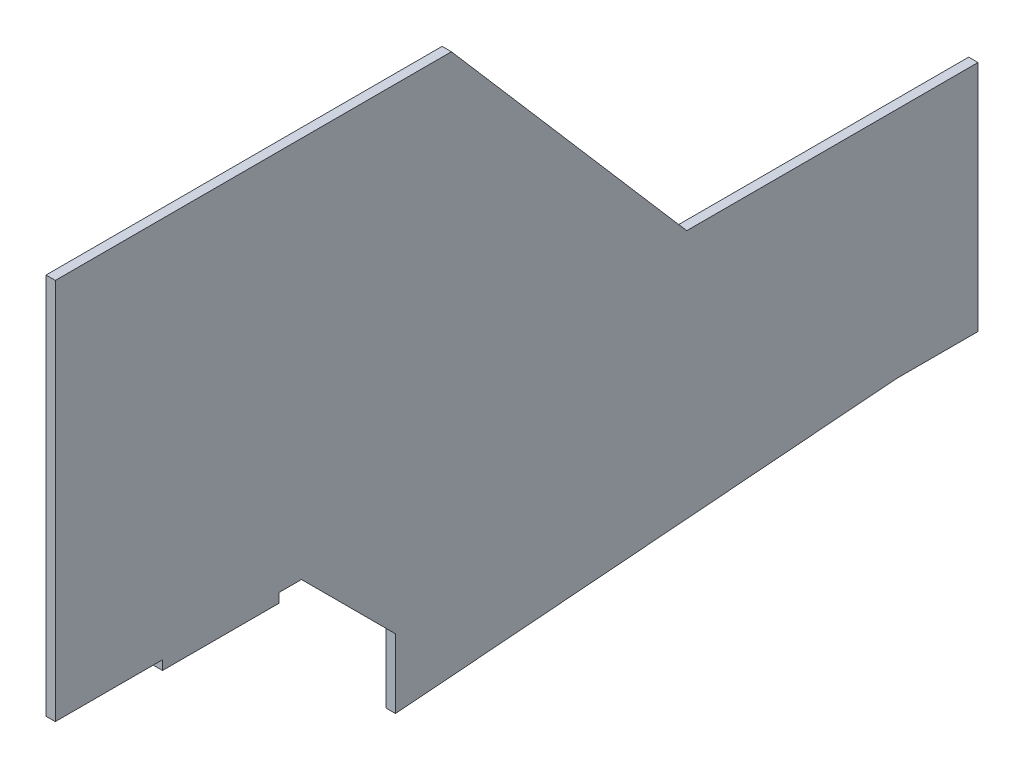
SolidWorks part; units mm, degrees
ref_plane "Alzado" through (0, 0, 0) normal (0, 0, 1) x (1, 0, 0)
ref_plane "Planta" through (0, 0, 0) normal (0, 1, 0) x (1, 0, 0)
ref_plane "Vista lateral" through (0, 0, 0) normal (1, 0, 0) x (0, 0, -1)
sketch "Croquis2" plane through (0, 0, 0) normal (1, 0, 0) x (0, 0, -1)
  line L0 (-196, -75) -> (-90.3534, -75)
  line L1 (-200, 150) -> (200, 150) construction
  line L2 (-200, 150) -> (-200, -150) construction
  line L3 (-200, -150) -> (200, -150) construction
  line L4 (200, 150) -> (200, -150) construction
  line L5 (-200, 150) -> (200, -150) construction
  line L6 (-200, -150) -> (200, 150) construction
  line L11 (-90.3534, -75) -> (-28.5398, -75) construction
  line L12 (-150, -75) -> (-150, -79) construction
  line L17 (-90.3534, -75) -> (-50, -115.3534)
  line L18 (-50, -115.3534) -> (-50, -145)
  line L19 (-50, -145) -> (165, -128)
  line L20 (165, -128) -> (200, -128)
  line L21 (200, -128) -> (200, -28)
  line L22 (200, -28) -> (75, -28)
  line L23 (75, -28) -> (-26, 89)
  line L24 (-26, 89) -> (-196, 89)
  line L25 (-196, 89) -> (-196, -75)
  line L26 (-150, -79) -> (-100, -79) construction
  line L27 (-100, -79) -> (-100, -75) construction
  line L29 (-150, -79) -> (-100, -79)
  line L30 (-150, -79) -> (-150, -55.6891)
  line L31 (-150, -55.6891) -> (-100, -55.6891)
  line L32 (-100, -79) -> (-100, -55.6891)
  line L33 (-150, -79) -> (-100, -55.6891) construction
  line L34 (-150, -55.6891) -> (-100, -79) construction
  point P0 (0, 0)
  point P10 (2, 0)
  point P23 (-125, -67.3446)
  dimension "D1" = 400
  dimension "D2" = 300
  dimension "D3" = 4
  dimension "D4" = 75
  dimension "D6" = 22
  dimension "D7" = 35
  dimension "D5" = 5
  dimension "D8" = 150
  dimension "D9" = 45
  dimension "D10" = 100
  dimension "D11" = 170
  dimension "D12" = 275
  dimension "D13" = 164
  dimension "D14" = 50
  dimension "D15" = 4
  dimension "D16" = 50
extrude "Saliente-Extruir1" add sketch "Croquis2" along normal blind 4 contours L32 L0 L17 L18 L19 L20 L21 L22 L23 L24 L25 L30 L31 | L0 L32 L31 L30 | L29 L32 L0 L30 region at (0, -31.7671, 17.2388) region at (0, -65.3446, 125) region at (0, -77, 125)
equation "\"venesta\"= 4'grosor de la venesta"
equation "\"policarbonato\"= 4'grosor del policarbonato"
equation "\"carton_trupan\"= 3'grosor del carton trupan caso laser"
equation "\"ancho_tot\"= 310'ancho tot sin llantas"
equation "\"largo_tot\"= 400'largo tot sin camera"
equation "\"alto_estimado\"= 300'alto estimado sin lidar"
equation "\"D2@Croquis2\"=\"alto_estimado\""
equation "\"D1@Croquis2\"=\"largo_tot\""
equation "\"altoparaqpaselabotella\"= 75'alto estimado para que encaje la botella"
equation "\"alturaruedaloca\"= 22"
equation "\"anchoruedaloca\"= 35"
equation "\"anchopiso1motorybaterias\"= 150"
equation "\"dist-pisorampa\"= 5"
equation "\"D3@Croquis2\"=\"venesta\""
equation "\"D4@Croquis2\"=\"altoparaqpaselabotella\""
equation "\"D6@Croquis2\"=\"alturaruedaloca\""
equation "\"D7@Croquis2\"=\"anchoruedaloca\""
equation "\"D5@Croquis2\"=\"dist-pisorampa\""
equation "\"D8@Croquis2\"=\"anchopiso1motorybaterias\""
equation "\"D10@Croquis2\"= \"paredtrasera\""
equation "\"D11@Croquis2\" = \"anchoultimopiso\""
equation "\"anchoultimopiso\"= 170"
equation "\"paredtrasera\"= 100"
equation "\"agarradorcanasta\"= 275'recolector"
equation "\"D12@Croquis2\"=\"agarradorcanasta\""
equation "\"D13@Croquis2\"= \"alturapiso1y2\" + \"venesta\" + \"alturapiso2y3\""
equation "\"alturapiso1y2\"= 80"
equation "\"alturapiso2y3\"= 80"
equation "\"D1@Saliente-Extruir1\"=\"policarbonato\""
equation "\"D15@Croquis2\"=\"venesta\""
